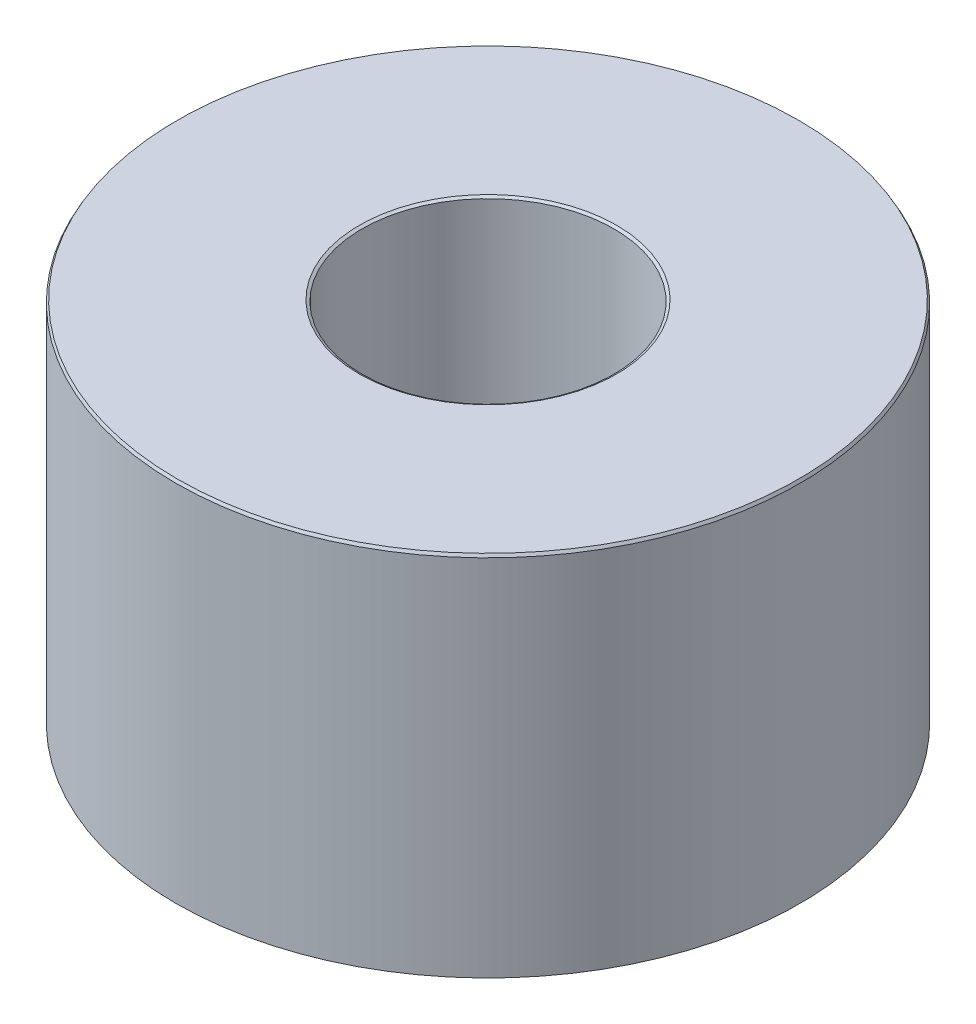
SolidWorks part; units mm, degrees
ref_plane "Front Plane" through (0, 0, 0) normal (0, 0, 1) x (1, 0, 0)
ref_plane "Top Plane" through (0, 0, 0) normal (0, 1, 0) x (1, 0, 0)
ref_plane "Right Plane" through (0, 0, 0) normal (1, 0, 0) x (0, 0, -1)
sketch "Sketch1" plane through (0, 0, 0) normal (0, 1, 0) x (1, 0, 0)
  circle A0 centre (0, 0) radius 22.5
  dimension "SLEEVE_OD" = 45
extrude "Boss-Extrude1" add sketch "Sketch1" along normal blind 26.5323
sketch "Sketch2" plane through (0, 0, 0) normal (0, 1, 0) x (1, 0, 0)
  circle A0 centre (0, 0) radius 9.0758
  dimension "BORE_D" = 18.1516
extrude "Cut-Extrude1" cut sketch "Sketch2" along normal through all
chamfer "Chamfer1" distance 0.201 angle 30 4 edges at (0, 26.5323, 9.0758) (0, 0, 9.0758) (0, 0, 22.5) (0, 26.5323, 22.5) first distance on face at (0, 26.5323, 9.0758) first distance on face at (0, 0, 9.0758) first distance on face at (0, 26.5323, 22.5)
